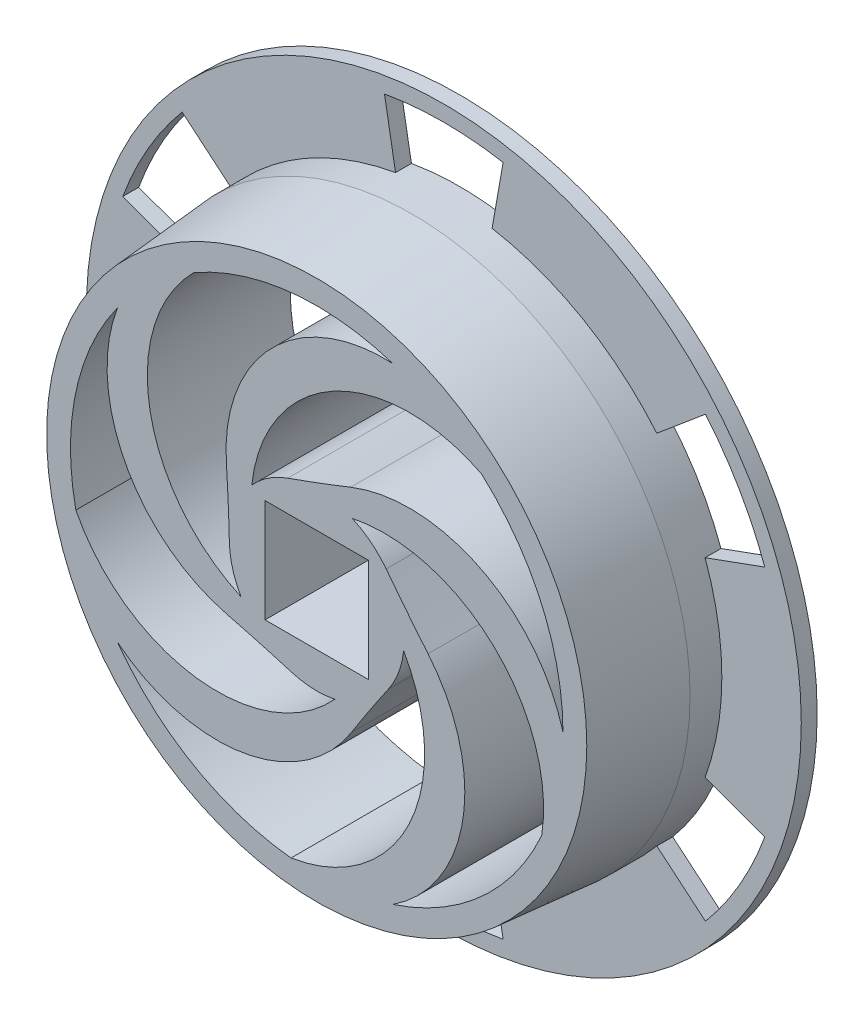
SolidWorks part; units mm, degrees
ref_plane "Front Plane" through (0, 0, 0) normal (0, 0, 1) x (1, 0, 0)
ref_plane "Top Plane" through (0, 0, 0) normal (0, 1, 0) x (1, 0, 0)
ref_plane "Right Plane" through (0, 0, 0) normal (1, 0, 0) x (0, 0, -1)
sketch "Sketch1" plane through (0, 0, 0) normal (0, 0, 1) x (1, 0, 0)
  circle A0 centre (0, 0) radius 22.5
  dimension "D1" = 45
extrude "Boss-Extrude1" add sketch "Sketch1" along normal blind 3
sketch "Sketch2" plane through (0, 0, 3) normal (0, 0, 1) x (1, 0, 0)
  circle A0 centre (0, 0) radius 17.5
  dimension "D1" = 35
extrude "Boss-Extrude2" add sketch "Sketch2" along normal blind 6
chamfer "Chamfer1" distance 6 distance2 0.5 1 edges at (17.5, 0, 9) first distance on face at (17.5, 0, 9)
sketch "Sketch3" plane through (0, 0, 9) normal (0, 0, 1) x (1, 0, 0)
  line L0 (0, 0) -> (0, 5.5) construction
  circle A0 centre (0, 0) radius 15.5
  circle A1 centre (0, 0) radius 5.5
  arc A2 (0, 5.5) -> (15.5, 0) centre (5.8472, -2.6123) cw
  arc A3 (2.2371, 5.0245) -> (14.16, -6.3044) centre (4.2792, -4.7648) cw
  arc A4 (4.0873, 3.6802) -> (10.3715, -11.5187) centre (1.9712, -6.0933) cw [skipped]
  arc A5 (5.2308, 1.6996) -> (4.7898, -14.7414) centre (-0.6776, -6.3683) cw
  arc A6 (5.4699, -0.5749) -> (-1.6202, -15.4151) centre (-3.2092, -5.5421) cw
  arc A7 (4.7631, -2.75) -> (-7.75, -13.4234) centre (-5.186, -3.7577) cw [skipped]
  arc A8 (3.2328, -4.4496) -> (-12.5398, -9.1107) centre (-6.266, -1.3235) cw
  arc A9 (1.1435, -5.3798) -> (-15.1613, -3.2226) centre (-6.2626, 1.3395) cw
  arc A10 (-1.1435, -5.3798) -> (-15.1613, 3.2226) centre (-5.1763, 3.7709) cw [skipped]
  arc A11 (-3.2328, -4.4496) -> (-12.5398, 9.1107) centre (-3.195, 5.5503) cw
  arc A12 (-4.7631, -2.75) -> (-7.75, 13.4234) centre (-0.6613, 6.37) cw
  arc A13 (-5.4699, -0.5749) -> (-1.6202, 15.4151) centre (1.9868, 6.0883) cw [skipped]
  arc A14 (-5.2308, 1.6996) -> (4.7898, 14.7414) centre (4.2914, 4.7538) cw
  arc A15 (-4.0873, 3.6802) -> (10.3715, 11.5187) centre (5.8539, 2.5974) cw
  arc A16 (-2.2371, 5.0245) -> (14.16, 6.3044) centre (6.4042, -0.0082) cw [skipped]
  point P7 (1.5401, -17.0786)
  point P14 (0, 0)
  point P15 (0, 0)
  dimension "D1" = 31
  dimension "D2" = 10
  dimension "D3" = 10
  dimension "D5" = 5.5
  dimension "D4" = 15
extrude "Cut-Extrude1" cut sketch "Sketch3" against normal up to next contours A15 A1 A2 A0 | A1 A5 A0 A3 | A1 A8 A0 A6 | A1 A11 A0 A9 | A1 A14 A0 A12 region at (9.2594, 7.0038, 9) region at (5.6102, 10.164, 9) region at (12.3728, -8.9894, 9) region at (7.6498, -13.2499, 9) region at (-3.8012, 10.9717, 9) region at (-7.9327, 8.4764, 9) region at (-4.7256, -14.5438, 9) region at (-10.234, -11.366, 9) region at (-11.6112, -0.226, 9) region at (-10.5137, -4.9264, 9)
fillet "Fillet1" radius 100 5 edges at (5.2308, 1.6996, 4.5) (3.2328, -4.4496, 4.5) (-3.2328, -4.4496, 4.5) (-5.2308, 1.6996, 4.5) (0, 5.5, 4.5)
sketch "Sketch4" plane through (0, 0, 9) normal (0, 0, 1) x (1, 0, 0)
  line L1 (-3.25, -3.25) -> (3.25, -3.25)
  line L2 (-3.25, -3.25) -> (-3.25, 3.25)
  line L3 (-3.25, 3.25) -> (3.25, 3.25)
  line L4 (3.25, -3.25) -> (3.25, 3.25)
  line L5 (-3.25, -3.25) -> (3.25, 3.25) construction
  line L6 (-3.25, 3.25) -> (3.25, -3.25) construction
  point P0 (0, 0)
  dimension "D1" = 6.5
extrude "Cut-Extrude2" cut sketch "Sketch4" against normal up to next
sketch "Sketch6" plane through (0, 0, 3) normal (0, 0, 1) x (1, 0, 0)
  circle A0 centre (0, 0) radius 17.5
  circle A1 centre (0, 0) radius 22.5
  circle A2 centre (0, 0) radius 17.5 construction
  dimension "D1" = 45
extrude "Cut-Extrude3" cut sketch "Sketch6" against normal blind 2
sketch "Sketch7" plane through (0, 0, 1) normal (0, 0, 1) x (1, 0, 0)
  line L0 (0, 0) -> (-3.7334, 21.1734) construction
  line L1 (0, 0) -> (3.7334, 21.1734) construction
  line L2 (0, 0) -> (0, 21.5) construction
  line L3 (-3.7334, 21.1734) -> (3.7334, 21.1734)
  line L4 (-3.7334, 21.1734) -> (-3.0388, 17.2341)
  line L5 (3.0388, 17.2341) -> (3.7334, 21.1734)
  circle A0 centre (0, 0) radius 21.5
  circle A1 centre (0, 0) radius 22.5 construction
  circle A2 centre (0, 0) radius 17.5
  circle A3 centre (0, 0) radius 17.5 construction
  arc A4 (-3.0388, 17.2341) -> (3.0388, 17.2341) centre (0, 0) cw
  point P10 (0, 21.1734)
  circle M2 centre (0, 0) radius 17.5
  dimension "D1" = 1
  dimension "D2" = 20
extrude "Cut-Extrude4" cut sketch "Sketch7" against normal up to next contours L5 L3 L4 M2 | L3 A0 region at (0, 21.3041, 1) region at (0, 19.3525, 1)
pattern_circular "CirPattern1" count 6 over 360 about axis through (0, 0, 3) along (0, 0, -1) of "Cut-Extrude4" reverse direction yes
